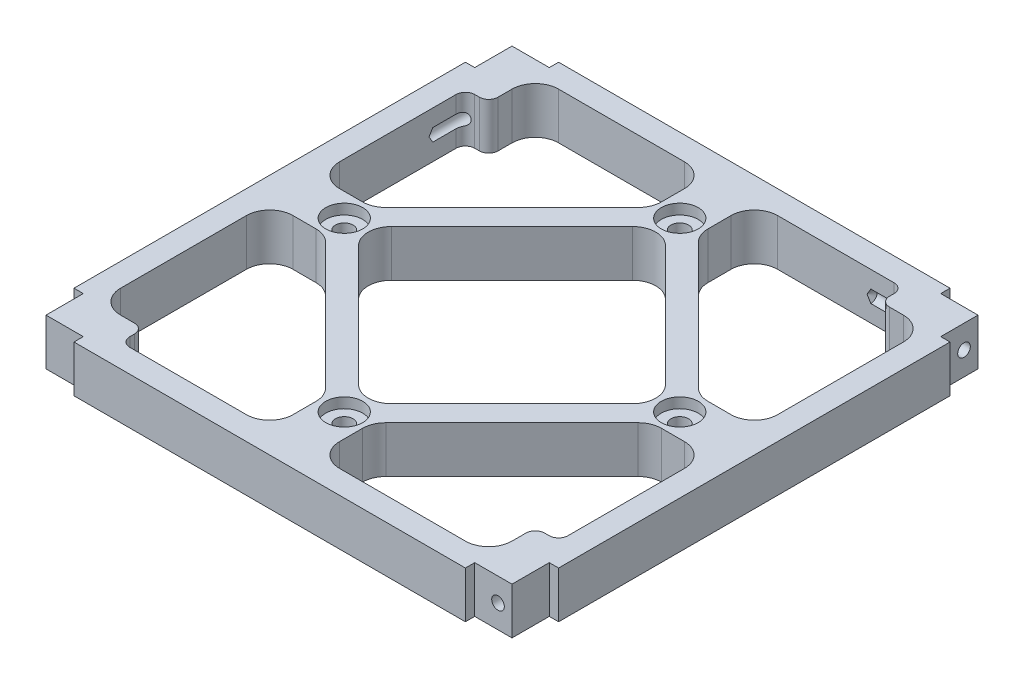
SolidWorks part; units mm, degrees
material "6061-T6 (SS)"
ref_plane "Front Plane" through (0, 0, 0) normal (0, 0, 1) x (1, 0, 0)
ref_plane "Top Plane" through (0, 0, 0) normal (0, 1, 0) x (1, 0, 0)
ref_plane "Right Plane" through (0, 0, 0) normal (1, 0, 0) x (0, 0, -1)
sketch "Sketch1" plane through (0, 0, 0) normal (0, 1, 0) x (1, 0, 0)
  line L0 (-42, 47) -> (-42, 37)
  line L1 (-52, 52) -> (52, 52)
  line L2 (-52, 52) -> (-52, -52)
  line L3 (-52, -52) -> (52, -52)
  line L4 (52, 52) -> (52, -52)
  line L5 (-47, 5) -> (-35, 5)
  line L6 (-35, 5) -> (-5, 35)
  line L7 (-5, 35) -> (-5, 47)
  line L8 (-5, 47) -> (-42, 47)
  line L9 (0, 0) -> (0, 76.3292) construction
  line L10 (0, 0) -> (-78.8537, 0) construction
  line L11 (0, 0) -> (-66.7994, 66.7994) construction
  line L12 (-32.9289, 0) -> (0, 32.9289)
  line L13 (0, 32.9289) -> (32.9289, 0)
  line L14 (32.9289, 0) -> (0, -32.9289)
  line L15 (0, -32.9289) -> (-32.9289, 0)
  line L16 (5, 47) -> (5, 35)
  line L17 (37, 47) -> (5, 47)
  line L18 (37, 42) -> (37, 47)
  line L19 (47, 42) -> (37, 42)
  line L20 (47, 5) -> (47, 42)
  line L21 (35, 5) -> (47, 5)
  line L22 (5, 35) -> (35, 5)
  line L23 (47, -5) -> (35, -5)
  line L24 (47, -37) -> (47, -5)
  line L25 (42, -37) -> (47, -37)
  line L26 (42, -47) -> (42, -37)
  line L27 (5, -47) -> (42, -47)
  line L28 (5, -35) -> (5, -47)
  line L29 (35, -5) -> (5, -35)
  line L30 (-5, -47) -> (-5, -35)
  line L31 (-42, 37) -> (-47, 37)
  line L32 (-47, 37) -> (-47, 5)
  line L33 (-37, -47) -> (-5, -47)
  line L34 (-37, -42) -> (-37, -47)
  line L35 (-47, -42) -> (-37, -42)
  line L36 (-47, -5) -> (-47, -42)
  line L37 (-35, -5) -> (-47, -5)
  line L38 (-5, -35) -> (-35, -5)
  point P36 (0.1996, 0.1996)
  point P45 (0, 0)
  dimension "D1" = 104
  dimension "D2" = 5
  dimension "D3" = 5
  dimension "D4" = 5
  dimension "D5" = 5
  dimension "D6" = 5
  dimension "D7" = 12
  dimension "D8" = 10
  dimension "D9" = 10
  dimension "D10" = 4
extrude "Boss-Extrude1" add sketch "Sketch1" along normal blind 10
fillet "Fillet1" radius 5 24 edges at (32.9289, 5, 0) (0, 5, 32.9289) (-32.9289, 5, 0) (0, 5, -32.9289) (-5, 5, -47) (-5, 5, -35) (-35, 5, -5) (-47, 5, 42) (-47, 5, 5) (-35, 5, 5) (-5, 5, 35) (-5, 5, 47) (42, 5, 47) (47, 5, 5) (35, 5, 5) (5, 5, 35) (5, 5, 47) (47, 5, -42) (47, 5, -5) (35, 5, -5) (5, 5, -35) (5, 5, -47) (-42, 5, -47) (-47, 5, -5)
sketch "Sketch2" plane through (0, 10, 0) normal (0, 1, 0) x (1, 0, 0)
  line L0 (-52, 52) -> (-42, 52)
  line L1 (52, 52) -> (-52, 52) construction
  line L2 (-42, 52) -> (-42, 50)
  line L3 (-42, 50) -> (-50, 50)
  line L4 (-50, 50) -> (-50, 42)
  line L5 (-50, 42) -> (-52, 42)
  line L6 (-52, 52) -> (-52, -52) construction
  line L7 (-52, 42) -> (-52, 52)
  dimension "D1" = 2
  dimension "D2" = 10
extrude "Cut-Extrude1" cut sketch "Sketch2" against normal through all
ref_axis "Axis1" through (0, 10.5, 0) along (0, -1, 0)
pattern_circular "CirPattern1" count 4 over 360 about axis through (0, 10.5, 0) along (0, -1, 0) of "Cut-Extrude1"
hole_wizard "CBORE for #6 Binding Head Machine Screw1" positions "Sketch3" profile "Sketch5" counterbore size "#6" standard "ANSI Inch" end condition through all
sketch "Sketch3" plane through (0, 10, 0) normal (0, 1, 0) x (1, 0, 0)
  line L2 (0, 36) -> (36, 0)
  line L3 (-36, 0) -> (0, -36)
  line L4 (36, 0) -> (0, -36)
  line L6 (0, 0) -> (0, 48.9753) construction
  line L7 (0, 0) -> (-18.2924, 0) construction
  line L9 (-36, 0) -> (0, 36)
  line L11 (-3.5355, 29.3934) -> (-29.3934, 3.5355) construction
  point P0 (0, 36)
  point P199 (-36, 0)
  point P315 (0, -36)
  point P316 (36, 0)
  dimension "D1" = 36
sketch "Sketch5" plane through (0, 10, -36) normal (1, 0, 0) x (0, 0, 1)
  line L0 (0, 0) -> (0, 10)
  line L1 (0, 10) -> (1.8986, 10)
  line L3 (1.8986, 10) -> (1.8987, 2.2098)
  line L4 (1.8987, 2.2098) -> (3.9687, 2.2098)
  line L5 (3.9687, 2.2098) -> (3.9687, 0)
  line L7 (3.9687, 0) -> (0, 0)
  line L11 (0, -6.35) -> (0, 107.95) construction
  dimension "Thru Hole Dia." = 3.7973
  dimension "Thru Hole Depth" = 10
  dimension "C'Bore Dia." = 7.9375
  dimension "C'Bore Depth" = 2.2098
fillet "Fillet3" radius 2 8 edges at (-37, 5, 42) (-37, 5, 47) (42, 5, 37) (47, 5, 37) (37, 5, -42) (37, 5, -47) (-47, 5, -37) (-42, 5, -37)
hole_wizard "#6-32 Tapped Hole1" positions "Sketch6" profile "Sketch9" tap size "#6-32" standard "ANSI Inch"
sketch "Sketch6" plane through (50, 0, 0) normal (1, 0, 0) x (0, 0, -1)
  line L2 (42, 10) -> (52, 0)
  point P0 (47, 5)
  point P13 (47, 5)
sketch "Sketch9" plane through (50, 5, -47) normal (0, 1, 0) x (0, 0, -1)
  line L0 (0, 0) -> (0, 20.8127)
  line L1 (0, 20.8127) -> (1.3525, 20)
  line L2 (1.3525, 20) -> (1.3525, 0)
  line L5 (1.3525, 0) -> (0, 0)
  line L10 (0, 20.8127) -> (-1.3526, 20) construction
  line L11 (0, -6.35) -> (0, 107.95) construction
  dimension "Tap Drill Dia." = 2.7051
  dimension "Tap Drill Depth" = 20
  dimension "Drill Angle" = 118
cosmetic thread "Hole Thread1" parameters "D1"=7.01, "D2"=3.5052
pattern_circular "CirPattern5" count 4 over 360 about axis through (0, 10.5, 0) along (0, -1, 0) of "#6-32 Tapped Hole1"
